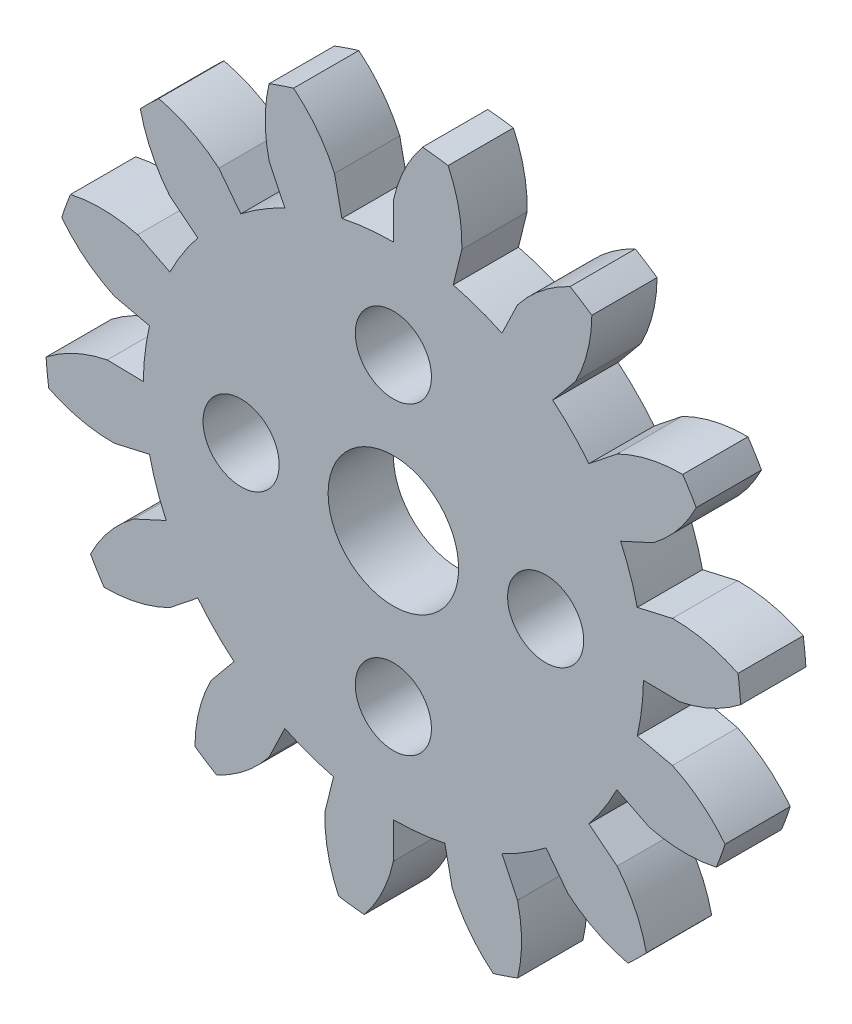
SolidWorks part; units mm, degrees
ref_plane "Plan de face" through (0, 0, 0) normal (0, 0, 1) x (1, 0, 0)
ref_plane "Plan de dessus" through (0, 0, 0) normal (0, 1, 0) x (1, 0, 0)
ref_plane "Plan de droite" through (0, 0, 0) normal (1, 0, 0) x (0, 0, -1)
sketch "Esquisse1" plane through (0, 0, 0) normal (0, 0, 1) x (1, 0, 0)
  circle A0 centre (0, 0) radius 14
  circle A1 centre (0, 0) radius 16
  circle A2 centre (0, 0) radius 11.5
  circle A3 centre (0, 0) radius 12
  circle A4 centre (0, 0) radius 13.1557
  dimension "Pitch Circle" = 28
  dimension "Addendum Circle" = 32
  dimension "Root Circle" = 23
  dimension "Clearence Circle" = 24
  dimension "Base Circle" = 26.3114
sketch "Involute" plane through (0, 0, 0) normal (0, 0, 1) x (1, 0, 0)
  line L0 (0, 0) -> (0, 13.1557)
  line L1 (0, 0) -> (6.5778, 11.3932) construction
  line L2 (0, 0) -> (11.3932, 6.5778) construction
  line L3 (0, 0) -> (13.1557, 0) construction
  line L4 (13.1557, 0) -> (13.1557, 20.6649) construction
  line L5 (11.3932, 6.5778) -> (4.5049, 18.5087) construction
  line L6 (6.5778, 11.3932) -> (0.6124, 14.8373) construction
  line L7 (0, 0) -> (3.1153, 13.649) construction
  line L8 (6.0744, 12.6136) -> (0, 0)
  line L9 (1.6873, 13.898) -> (0, 0) construction
  circle A0 centre (0, 0) radius 13.1557 construction
  circle A1 centre (0, 0) radius 14 construction
  arc A2 (3.1153, 13.649) -> (0.2412, 13.9979) centre (0, 0) ccw
  spline S0 degree 3 poles (0, 13.1557) (1.1572, 18.5432) (8.7162, 20.6719) (13.1557, 20.6649) knots 0 0 0 0 1 1 1 1
  spline S1 degree 3 poles (3.1479, 12.7735) (3.3134, 18.2814) (-3.5166, 22.1571) (-7.8288, 23.2125) knots 0 0 0 0 1 1 1 1
  dimension "Involute Control" = 90
  dimension "Base Circle Quarter Circumference" = 20.6649
  dimension "D1" = 13.7766
  dimension "D2" = 6.8883
  dimension "Circular Pitch" = 25.714
  dimension "Involute Array" = 4
sketch "Esquisse4" plane through (0, 0, 0) normal (0, 0, 1) x (1, 0, 0)
  line L0 (0, 0) -> (0, 13.1557) construction
  line L1 (0, 13.1557) -> (0, 11.5)
  line L2 (3.1479, 12.7735) -> (2.7518, 11.1659)
  arc A0 (1.3368, 15.9441) -> (2.5172, 15.8007) centre (0, 0) cw
  circle A1 centre (0, 0) radius 16 construction
  arc A2 (0, 11.5) -> (2.7518, 11.1659) centre (0, 0) cw
  circle A3 centre (0, 0) radius 11.5 construction
  arc A4 (0, 13.1557) -> (1.3368, 15.9441) centre (6.5215, 11.7438) cw
  arc A5 (2.5172, 15.8007) -> (3.1479, 12.7735) centre (-3.522, 12.9632) cw
  spline S0 degree 3 poles (0, 13.1557) (1.1572, 18.5432) (8.7162, 20.6719) (13.1557, 20.6649) knots 0 0 0 0 1 1 1 1 construction
  spline S1 degree 3 poles (3.1479, 12.7735) (3.3134, 18.2814) (-3.5166, 22.1571) (-7.8288, 23.2125) knots 0 0 0 0 1 1 1 1 construction
extrude "Boss.-Extru.1" add sketch "Esquisse4" along normal blind 3
ref_axis "Axe1" through (0, 0, 0) along (0, 0, 1)
pattern_circular "Répétition circulaire2" count 14 over 360 about axis through (0, 0, 0) along (0, 0, 1) of bodies 101
sketch "Esquisse5" plane through (0, 0, 0) normal (0, 0, 1) x (1, 0, 0)
  circle A0 centre (0, 0) radius 11.5 construction
  circle A1 centre (0, 0) radius 11.5
extrude "Boss.-Extru.2" add sketch "Esquisse5" along normal up to surface (3 mm away) up to face at (-9.4798, 9.6446, 3)
sketch "Esquisse6" plane through (0, 0, 0) normal (0, 0, -1) x (-1, 0, 0)
  line L0 (0, 0) -> (0, 7) construction
  circle A0 centre (0, 0) radius 3
  circle A1 centre (0, 7) radius 1.75
  circle A2 centre (7, 0) radius 1.75
  circle A3 centre (0, -7) radius 1.75
  circle A4 centre (-7, 0) radius 1.75
  point P5 (0, 0)
  point P6 (0, -6.67)
  dimension "D1" = 3.5
  dimension "D4" = 6
  dimension "D3" = 7
  dimension "D2" = 4
extrude "Enlèv. mat.-Extru.1" cut sketch "Esquisse6" against normal through all
equation "\"Module\"= 2"
equation "\"Nb de dents\"= 14"
equation "\"Pressure Angle\"= 20"
equation "\"Pitch Circle@Esquisse1\"= \"Module\" * \"Nb de dents\""
equation "\"Addendum Circle@Esquisse1\"= \"Pitch Circle@Esquisse1\" + ( \"Module\" * 2 )"
equation "\"Clearence Circle@Esquisse1\"= \"Pitch Circle@Esquisse1\" - ( \"Module\" * 2 )"
equation "\"Root Circle@Esquisse1\"= \"Pitch Circle@Esquisse1\" - ( ( \"Module\" * 1.25 ) * 2 )"
equation "\"Base Circle@Esquisse1\"= \"Pitch Circle@Esquisse1\" * cos ( \"Pressure Angle\" )"
equation "\"Base Circle Quarter Circumference@Involute\" = \"Base Circle@Esquisse1\" * pI / 4"
equation "\"D1@Involute\"=\"Base Circle Quarter Circumference@Involute\"/3*2"
equation "\"D2@Involute\"=\"Base Circle Quarter Circumference@Involute\"/3"
equation "\"Circular Pitch@Involute\"=360/\"Nb de dents\""
equation "\"D1@Répétition circulaire2\"= \"Nb de dents\""
